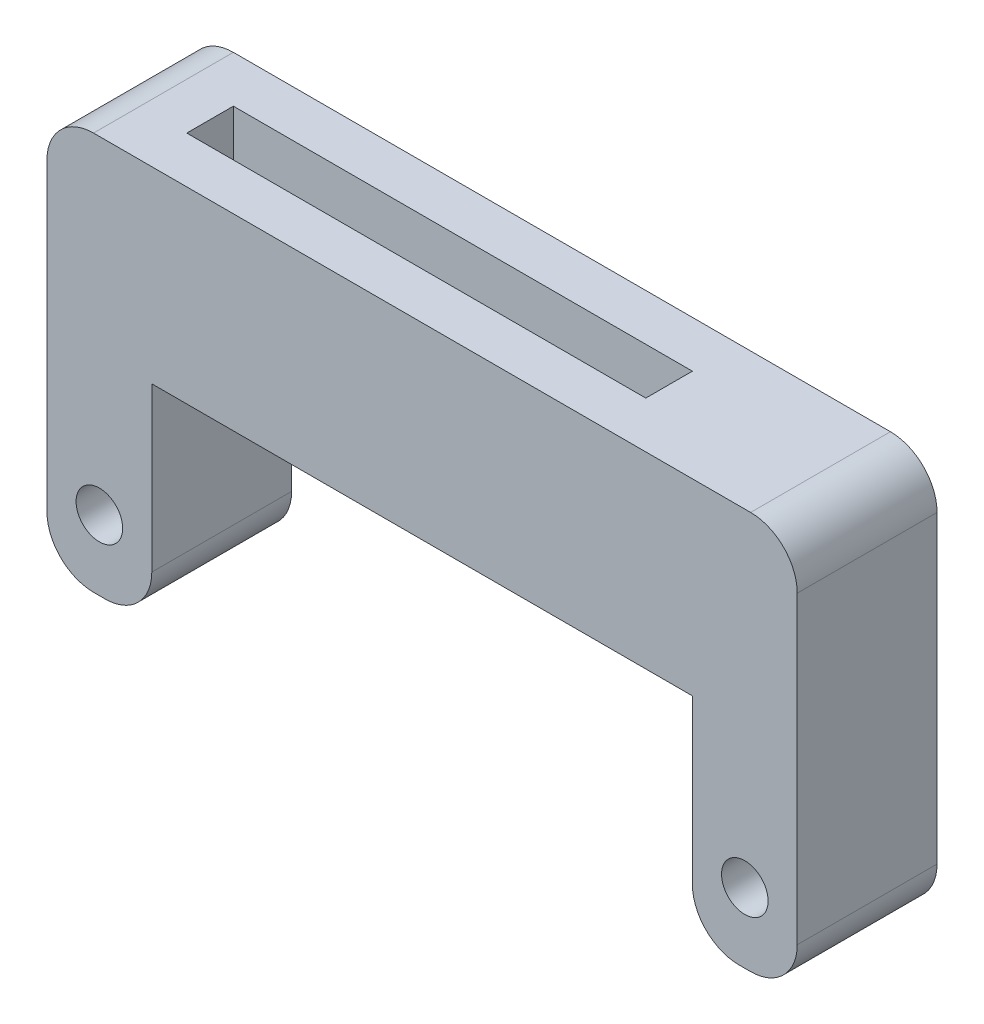
SolidWorks part; units mm, degrees
ref_plane "Front Plane" through (0, 0, 0) normal (0, 0, 1) x (1, 0, 0)
ref_plane "Top Plane" through (0, 0, 0) normal (0, 1, 0) x (1, 0, 0)
ref_plane "Right Plane" through (0, 0, 0) normal (1, 0, 0) x (0, 0, -1)
sketch "Sketch2" plane through (0, 0, 0) normal (0, 0, 1) x (1, 0, 0)
  line L1 (-16.1, -8.534) -> (16.1, -8.534)
  line L2 (-16.1, -8.534) -> (-16.1, 8.534)
  line L3 (-16.1, 8.534) -> (16.1, 8.534)
  line L4 (16.1, -8.534) -> (16.1, 8.534)
  line L5 (-16.1, -8.534) -> (16.1, 8.534) construction
  line L6 (-16.1, 8.534) -> (16.1, -8.534) construction
  point P0 (0, 0)
  dimension "D1" = 17.068
  dimension "D2" = 32.2
extrude "Boss-Extrude1" add sketch "Sketch2" along normal mid plane 6
sketch "Sketch3" plane through (0, 8.534, 0) normal (0, 1, 0) x (1, 0, 0)
  line L0 (-16.1, -3) -> (-16.1, 3) construction
  line L1 (-12.1, 1) -> (7.6, 1)
  line L2 (-12.1, 1) -> (-12.1, -1)
  line L3 (-12.1, -1) -> (7.6, -1)
  line L4 (7.6, 1) -> (7.6, -1)
  line L5 (16.1, -3) -> (16.1, 3) construction
  line L6 (16.1, 3) -> (-16.1, 3) construction
  dimension "D1" = 2
  dimension "D2" = 4
  dimension "D3" = 8.5
  dimension "D4" = 2
extrude "Cut-Extrude1" cut sketch "Sketch3" against normal blind 5
sketch "Sketch4" plane through (0, 0, 3) normal (0, 0, 1) x (1, 0, 0)
  line L0 (-16.1, -8.534) -> (16.1, -8.534) construction
  line L1 (-11.6, -8.534) -> (11.6, -8.534)
  line L2 (-11.6, -8.534) -> (-11.6, 0.466)
  line L3 (-11.6, 0.466) -> (11.6, 0.466)
  line L4 (11.6, -8.534) -> (11.6, 0.466)
  line L5 (-16.1, 8.534) -> (-16.1, -8.534) construction
  line L6 (16.1, -8.534) -> (16.1, 8.534) construction
  dimension "D1" = 9
  dimension "D2" = 4.5
  dimension "D3" = 4.5
extrude "Cut-Extrude2" cut sketch "Sketch4" against normal through all
sketch "Sketch5" plane through (0, 0, 3) normal (0, 0, 1) x (1, 0, 0)
  line L0 (-16.1, 8.534) -> (-16.1, -8.534) construction
  line L1 (16.1, -8.534) -> (16.1, 8.534) construction
  line L2 (-16.1, -8.534) -> (-11.6, -8.534) construction
  circle A0 centre (-13.85, -5.534) radius 1
  circle A2 centre (13.85, -5.534) radius 1
  dimension "D1" = 2
  dimension "D2" = 2.25
  dimension "D3" = 2.25
  dimension "D4" = 3
extrude "Cut-Extrude3" cut sketch "Sketch5" against normal through all
fillet "Fillet1" radius 2 6 edges at (-16.1, -8.534, 0) (-11.6, -8.534, 0) (11.6, -8.534, 0) (16.1, -8.534, 0) (16.1, 8.534, 0) (-16.1, 8.534, 0)
